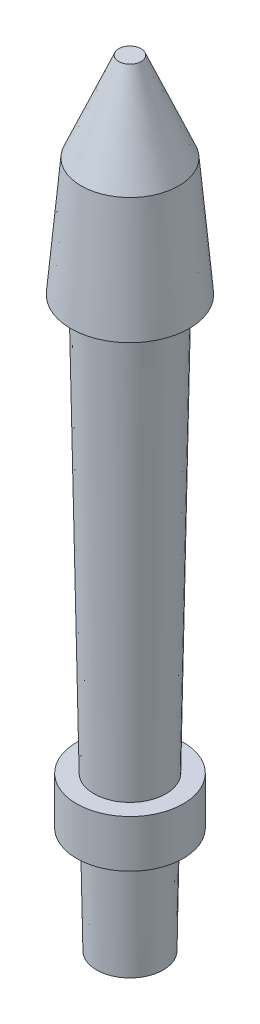
SolidWorks part; units mm, degrees
note: The reader was unsure of these and kept them because the rebuilt part matched: shared geometry of "Sketch1<2>".
ref_plane "前视基准面" through (0, 0, 0) normal (0, 0, 1) x (1, 0, 0)
ref_plane "上视基准面" through (0, 0, 0) normal (0, 1, 0) x (1, 0, 0)
ref_plane "右视基准面" through (0, 0, 0) normal (1, 0, 0) x (0, 0, -1)
other "Configuration Table"
sketch "Sketch1" plane through (0, 0, 0) normal (0, 1, 0) x (1, 0, 0)
  circle A0 centre (0, 0) radius 6.075
  circle A1 centre (0, 0) radius 9
extrude "Boss-Extrude1" add sketch "Sketch1" against normal blind 8
extrude "Boss-Extrude2" add sketch "Sketch1<2>" along normal blind 70 draft 1 and the other way blind 26 draft 1 separate body contours A0
sketch "Sketch1<2>" plane through (0, 0, 0) normal (0, 1, 0) x (1, 0, 0) same geometry as "Sketch1"
sketch "Sketch4" plane through (0, 70, 0) normal (0, 1, 0) x (1, 0, 0)
  circle A0 centre (0, 0) radius 10
extrude "Boss-Extrude3" add sketch "Sketch4" along normal blind 20 draft 5
sketch "Sketch5" plane through (0, 90, 0) normal (0, 1, 0) x (1, 0, 0)
  circle A0 centre (0, 0) radius 8.2502
extrude "Boss-Extrude4" add sketch "Sketch5" along normal blind 15 draft 23
